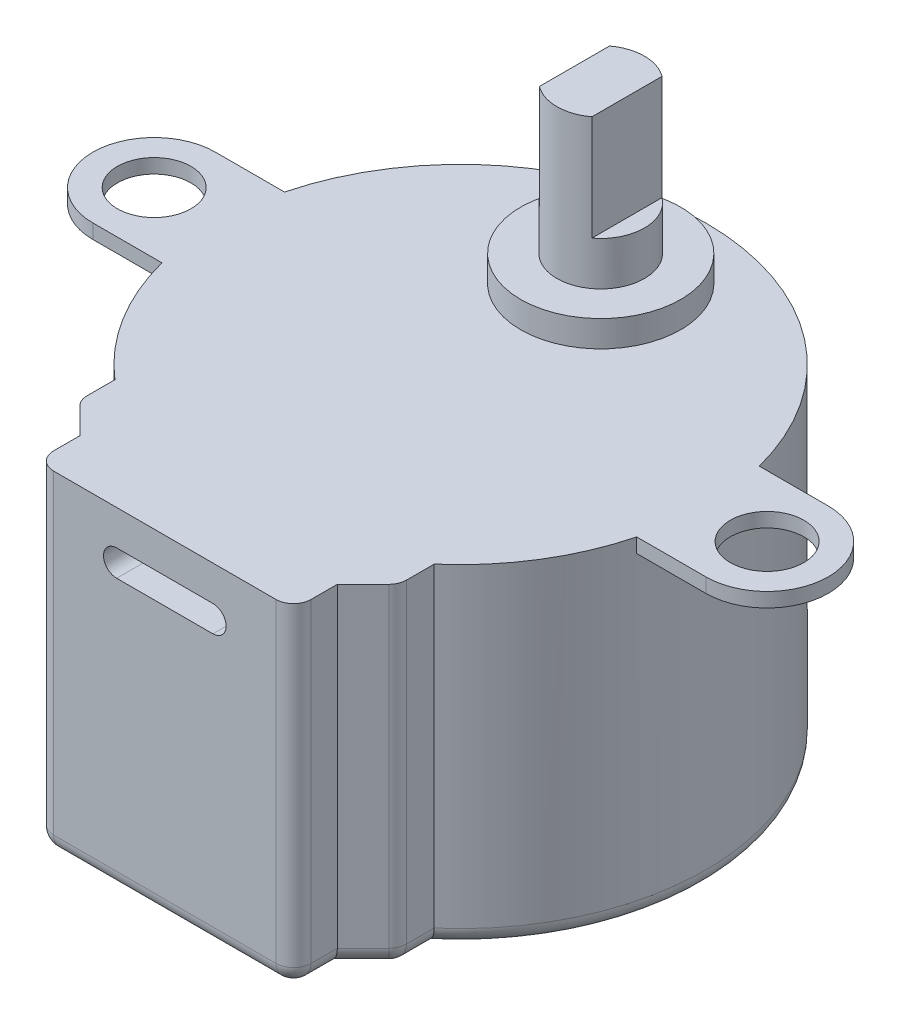
SolidWorks part; units mm, degrees
material "Galvanized Steel"
ref_plane "Front Plane" through (0, 0, 0) normal (0, 0, 1) x (1, 0, 0)
ref_plane "Top Plane" through (0, 0, 0) normal (0, 1, 0) x (1, 0, 0)
ref_plane "Right Plane" through (0, 0, 0) normal (1, 0, 0) x (0, 0, -1)
sketch "Sketch1" plane through (0, 0, 0) normal (0, 1, 0) x (1, 0, 0)
  line L0 (0, 0) -> (0, 60.1731) construction
  circle A0 centre (0, 0) radius 4.57
  dimension "D1" = 9.14
extrude "Boss-Extrude1" add sketch "Sketch1" along normal blind 1.5
sketch "Sketch2" plane through (0, 1.5, 0) normal (0, 1, 0) x (1, 0, 0)
  circle A0 centre (0, 0) radius 2.5
  dimension "D1" = 5
extrude "Boss-Extrude2" add sketch "Sketch2" along normal blind 2.5
sketch "Sketch3" plane through (0, 4, 0) normal (0, 1, 0) x (1, 0, 0)
  line L0 (0, 0) -> (0, 2.5) construction
  line L1 (1.5, 2) -> (1.5, -2)
  line L2 (0, 0) -> (1.5, 0) construction
  line L3 (-1.5, 2) -> (-1.5, -2)
  arc A0 (-1.5, 2) -> (1.5, 2) centre (0, 0) cw
  arc A1 (-1.5, -2) -> (1.5, -2) centre (0, 0) ccw
  dimension "D1" = 2.5
  dimension "D2" = 1.5
extrude "Boss-Extrude3" add sketch "Sketch3" along normal blind 6
sketch "Sketch4" plane through (0, 0, 0) normal (0, 1, 0) x (1, 0, 0)
  line L0 (0, -8) -> (0, 0) construction
  line L1 (0, -8) -> (0, -24.8916) construction
  line L2 (-6.35, -24.8916) -> (6.35, -24.8916)
  line L3 (7.35, -23.8916) -> (7.35, -22.3916)
  line L4 (7.35, -22.3916) -> (8.8249, -20.9167)
  line L5 (9.1178, -20.2096) -> (9.1178, -18.6239)
  line L6 (-9.1178, -20.2096) -> (-9.1178, -18.6239)
  line L7 (-7.35, -22.3916) -> (-8.8249, -20.9167)
  line L8 (-7.35, -23.8916) -> (-7.35, -22.3916)
  arc A0 (8.8249, -20.9167) -> (9.1178, -20.2096) centre (8.1178, -20.2096) ccw
  arc A1 (9.1178, -18.6239) -> (-9.1178, -18.6239) centre (0, -8) ccw
  arc A2 (6.35, -24.8916) -> (7.35, -23.8916) centre (6.35, -23.8916) ccw
  arc A3 (-8.8249, -20.9167) -> (-9.1178, -20.2096) centre (-8.1178, -20.2096) cw
  arc A4 (-6.35, -24.8916) -> (-7.35, -23.8916) centre (-6.35, -23.8916) cw
  point P11 (9.1178, -20.6239)
  point P14 (7.35, -24.8916)
  dimension "D1" = 14
  dimension "D8" = 1
  dimension "D2" = 8
  dimension "D3" = 7.35
  dimension "D4" = 2.5
  dimension "D5" = 45
  dimension "D6" = 2.5
  dimension "D7" = 2
extrude "Boss-Extrude4" add sketch "Sketch4" against normal blind 19
fillet "Fillet1" radius 1 12 edges at (8.0874, -19, 21.6542) (9.0416, -19, 20.5923) (-7.35, -19, 23.1416) (-7.0571, -19, 24.5987) (7.35, -19, 23.1416) (7.0571, -19, 24.5987) (-8.0874, -19, 21.6542) (-9.0416, -19, 20.5923) (9.1178, -19, 19.4167) (0, -19, 24.8916) (-9.1178, -19, 19.4167) (0, -19, -6)
sketch "Sketch5" plane through (0, 0, 0) normal (0, 1, 0) x (1, 0, 0)
  line L0 (13.5554, -4.5) -> (17.5, -4.5)
  line L1 (17.5, -11.5) -> (13.5554, -11.5)
  line L2 (17.5, -8) -> (0, -8) construction
  line L3 (0, -8) -> (0, -24.8916) construction
  line L4 (0, -8) -> (0, 7.3617) construction
  line L5 (-17.5, -11.5) -> (-13.5554, -11.5)
  line L6 (-13.5554, -4.5) -> (-17.5, -4.5)
  arc A0 (17.5, -4.5) -> (17.5, -11.5) centre (17.5, -8) cw
  arc A1 (9.1178, -18.6239) -> (-9.1178, -18.6239) centre (0, -8) ccw construction
  circle A2 centre (17.5, -8) radius 2.1
  arc A3 (13.5554, -4.5) -> (13.5554, -11.5) centre (0, -8) cw
  arc A4 (-13.5554, -4.5) -> (-13.5554, -11.5) centre (0, -8) ccw
  circle A5 centre (-17.5, -8) radius 2.1
  arc A6 (-17.5, -4.5) -> (-17.5, -11.5) centre (-17.5, -8) ccw
  dimension "D1" = 7
  dimension "D3" = 4.2
  dimension "D2" = 17.5
extrude "Boss-Extrude5" add sketch "Sketch5" against normal blind 0.82
sketch "Sketch6" plane through (0, 0, 24.8916) normal (0, 0, 1) x (1, 0, 0)
  line L0 (-2.75, -2) -> (2.75, -2)
  line L1 (2.75, -3.5) -> (-2.75, -3.5)
  line L2 (0, -2) -> (0, 0) construction
  arc A0 (2.75, -2) -> (2.75, -3.5) centre (2.75, -2.75) cw
  arc A1 (-2.75, -3.5) -> (-2.75, -2) centre (-2.75, -2.75) cw
  dimension "D1" = 1.5
  dimension "D2" = 5.5
  dimension "D3" = 2
extrude "Cut-Extrude1" cut sketch "Sketch6" against normal blind 2
sketch "Sketch7" plane through (0, 0, 0) normal (0, 1, 0) x (1, 0, 0)
  line L0 (-17.5, -8) -> (0, -8)
  line L1 (0, -8) -> (0, 0)
